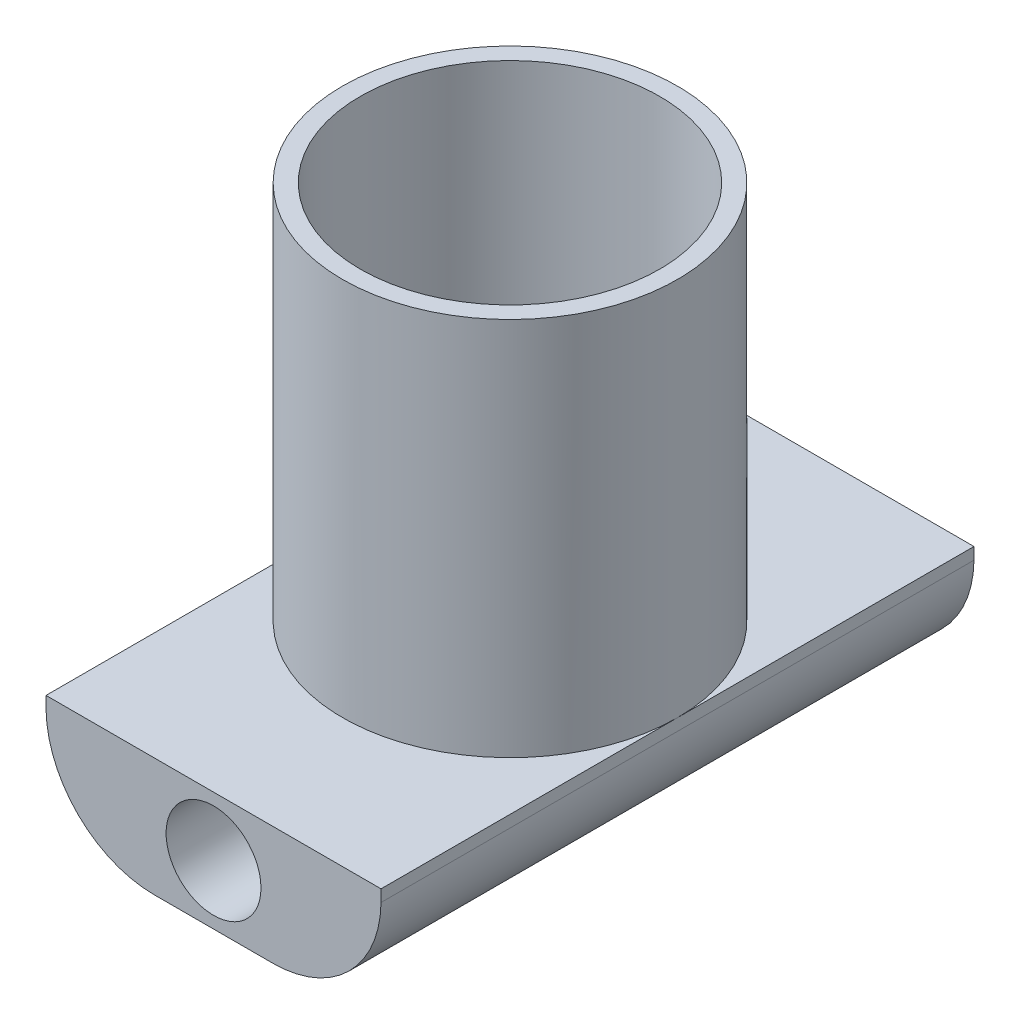
SolidWorks part; units mm, degrees
material "6063-T5"
ref_plane "Front Plane" through (0, 0, 0) normal (0, 0, 1) x (1, 0, 0)
ref_plane "Top Plane" through (0, 0, 0) normal (0, 1, 0) x (1, 0, 0)
ref_plane "Right Plane" through (0, 0, 0) normal (1, 0, 0) x (0, 0, -1)
sketch "Sketch1" plane through (0, 0, 0) normal (0, 1, 0) x (1, 0, 0)
  circle A0 centre (0, 0) radius 14.125
  circle A1 centre (0, 0) radius 12.625
  dimension "D1" = 28.25
  dimension "D2" = 25.25
extrude "Boss-Extrude1" add sketch "Sketch1" along normal blind 30
sketch "Sketch2" plane through (0, 0, 0) normal (0, -1, 0) x (-1, 0, 0)
  circle A0 centre (0, 0) radius 14.125
extrude "Boss-Extrude2" add sketch "Sketch2" along normal blind 3
sketch "Sketch3" plane through (0, 0, 0) normal (0, 0, 1) x (1, 0, 0)
  line L0 (0, 0) -> (0, -3)
  line L1 (0, -3) -> (0, -11)
  line L2 (0, -2) -> (14.125, -2)
  line L3 (14.125, -3) -> (14.125, 30) construction
  line L4 (14.125, -2) -> (14.125, -3)
  line L5 (0, -11) -> (7.5, -11)
  line L6 (0, -12) -> (5, -12)
  line L7 (0, -2) -> (-14.125, -2)
  line L8 (-14.125, 30) -> (-14.125, -3) construction
  line L9 (-14.125, -2) -> (-14.125, -3)
  line L10 (0, -12) -> (-5, -12)
  circle A0 centre (0, -7) radius 4
  circle A1 centre (0, -7) radius 5
  arc A2 (14.125, -3) -> (5, -12) centre (5, -2.8741) cw
  arc A3 (-14.125, -3) -> (-5, -12) centre (-5, -2.8741) ccw
  dimension "D3" = 10
  dimension "D1" = 3
  dimension "D2" = 8
  dimension "D4" = 7.5
  dimension "D5" = 5
  dimension "D6" = 5
extrude "Boss-Extrude3" add sketch "Sketch3" along normal blind 25 and the other way blind 25 contours L9 A3 L10 A1 L7 | L0 A1 L5 A0 | A2 L4 L2 A1 L6 | L5 A1 L0 A0 region at (3.4627, -3.5373, 0) region at (-8.302, -6.3708, 0) region at (8.302, -6.3708, 0) region at (-0.1281, -2.5, 0)
